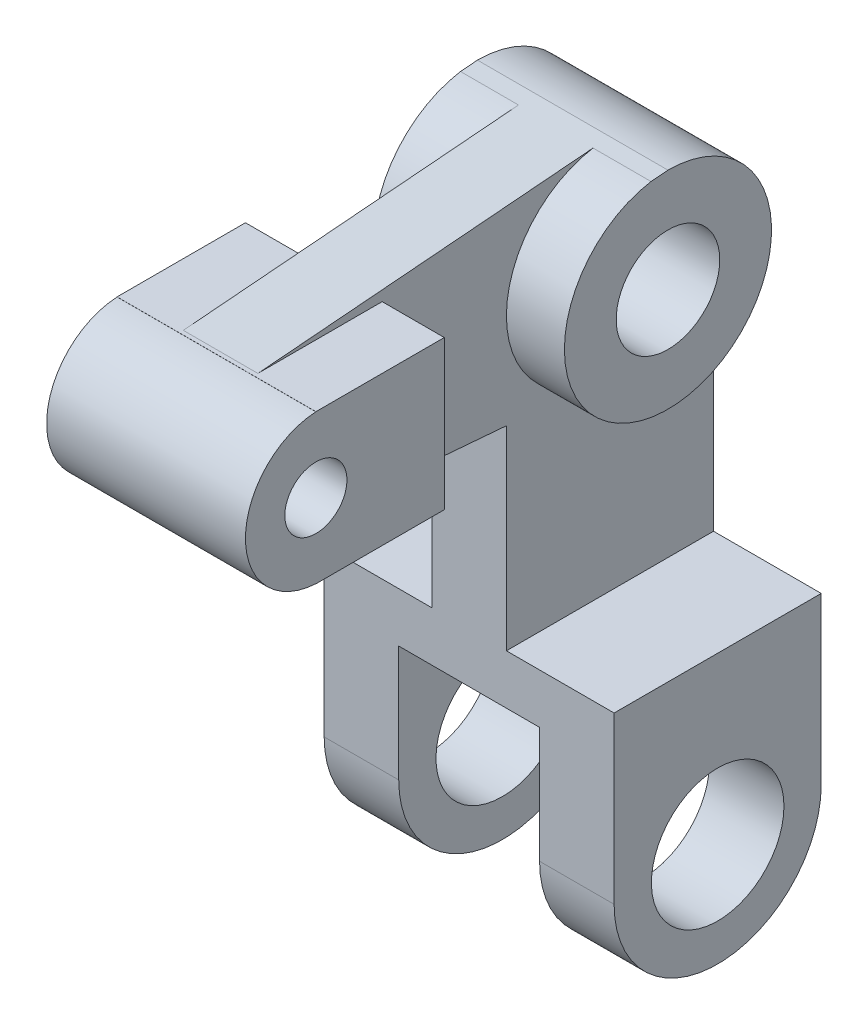
SolidWorks part; units mm, degrees
ref_plane "Plano frontal" through (0, 0, 0) normal (0, 0, 1) x (1, 0, 0)
ref_plane "Plano superior" through (0, 0, 0) normal (0, 1, 0) x (1, 0, 0)
ref_plane "Plano direito" through (0, 0, 0) normal (1, 0, 0) x (0, 0, -1)
sketch "Esboço1" plane through (0, 0, 0) normal (1, 0, 0) x (0, 0, -1)
  line L0 (-62.2573, 0) -> (55.5718, 0) construction
  line L1 (0, 169.4232) -> (0, -61.0604) construction
  line L3 (25, 110) -> (25, 0)
  line L4 (-25, 0) -> (-25, 87.0588)
  line L5 (-85, 128) -> (0, 135)
  line L6 (-85, 92) -> (-25, 87.0588)
  line L7 (-25, 40) -> (25, 40)
  arc A0 (-25, 0) -> (25, 0) centre (0, 0) ccw
  circle A1 centre (0, 0) radius 16
  circle A2 centre (0, 110) radius 25
  circle A3 centre (0, 110) radius 12.5
  circle A4 centre (-85, 110) radius 18
  circle A5 centre (-85, 110) radius 7.5
  dimension "D1" = 50
  dimension "D2" = 32
  dimension "D3" = 50
  dimension "D4" = 25
  dimension "D5" = 36
  dimension "D6" = 15
  dimension "D7" = 110
  dimension "D8" = 85
  dimension "D9" = 40
extrude "Ressalto-extrusão1" add sketch "Esboço1" along normal mid plane 48 contours A4 A5 region at (0, 122.3679, 72.6321)
extrude "Ressalto-extrusão2" add sketch "Esboço1<3>" along normal mid plane 18 contours A4 L6 L4 L7 L3 A2 L5 region at (0, 85.9315, 20.7557)
sketch "Esboço1<3>" plane through (0, 0, 0) normal (1, 0, 0) x (0, 0, -1) same geometry as "Esboço1"
extrude "Ressalto-extrusão3" add sketch "Esboço1<4>" along normal mid plane 46 contours A2 L5 A3 region at (0, 91.4704, 15.7099)
sketch "Esboço1<4>" plane through (0, 0, 0) normal (1, 0, 0) x (0, 0, -1) same geometry as "Esboço1"
extrude "Ressalto-extrusão4" add sketch "Esboço1<5>" along normal mid plane 70 contours A0 L3 L7 L4 region at (0, 20, -24.1799)
sketch "Esboço1<5>" plane through (0, 0, 0) normal (1, 0, 0) x (0, 0, -1) same geometry as "Esboço1"
sketch "Esboço2" plane through (0, 0, 0) normal (0, 0, 1) x (1, 0, 0)
  line L6 (-35, 0) -> (-35, 40) construction
  line L7 (-17, 28) -> (17, 28)
  line L8 (-17, 28) -> (-17, -38.3099)
  line L9 (-17, -38.3099) -> (17, -38.3099)
  line L10 (17, 28) -> (17, -38.3099)
  line L11 (35, 40) -> (9, 40) construction
  dimension "D1" = 18
  dimension "D2" = 34
  dimension "D3" = 12
extrude "Corte-extrusão1" cut sketch "Esboço2" against normal mid plane 140
ref_plane "Plano1" through (0, 0, 55) normal (0, 0, 1) x (1, 0, 0)
sketch "Esboço3" plane through (0, 0, 55) normal (0, 0, 1) x (1, 0, 0)
  line L1 (-24, 128) -> (24, 128)
  line L2 (-24, 128) -> (-24, 92)
  line L3 (-24, 92) -> (24, 92)
  line L4 (24, 128) -> (24, 92)
extrude "Ressalto-extrusão7" add sketch "Esboço3" along normal blind 31
sketch "Esboço4" plane through (0, 0, 0) normal (1, 0, 0) x (0, 0, -1)
  line L0 (-86, 102.567) -> (-86, 117.433) construction
  circle A0 centre (-86, 110) radius 7.5
  dimension "D1" = 15
extrude "Corte-extrusão2" cut sketch "Esboço4" against normal mid plane 97
